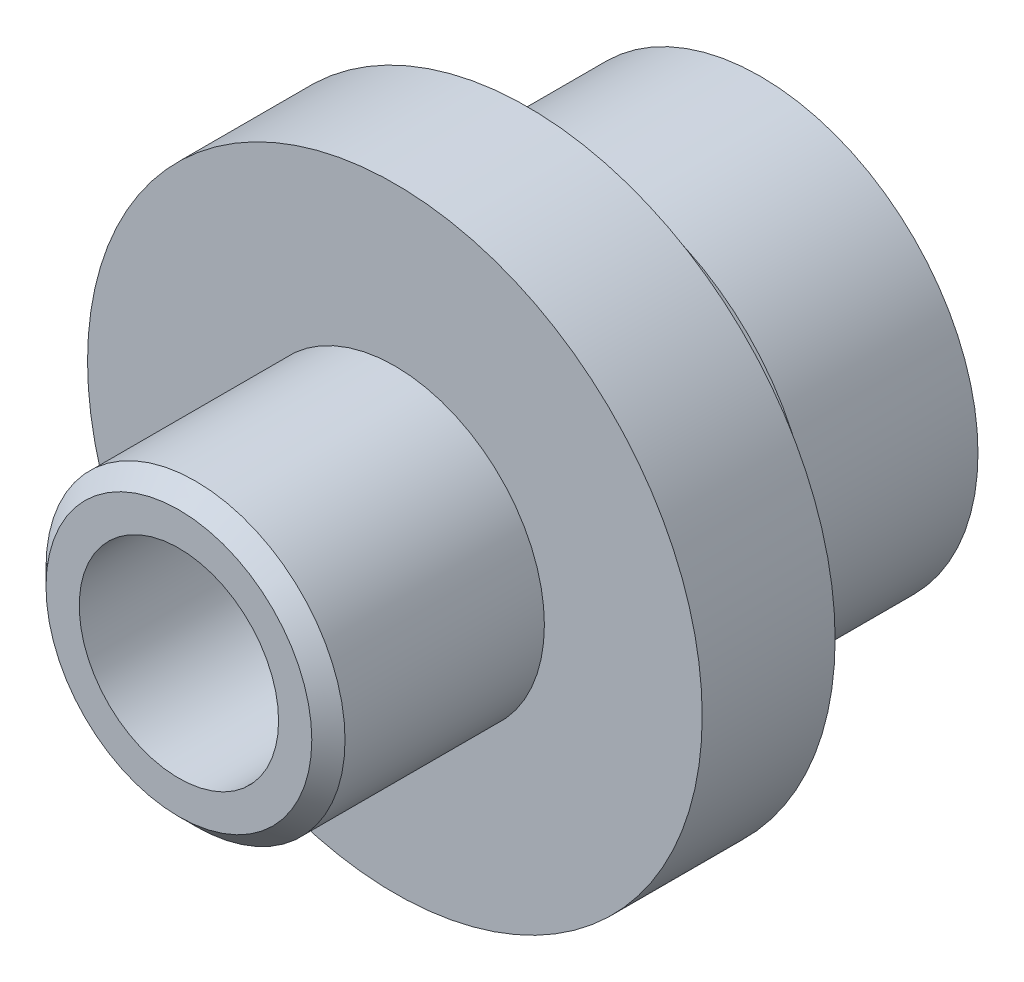
SolidWorks part; units mm, degrees
ref_plane "Front Plane" through (0, 0, 0) normal (0, 0, 1) x (1, 0, 0)
ref_plane "Top Plane" through (0, 0, 0) normal (0, 1, 0) x (1, 0, 0)
ref_plane "Right Plane" through (0, 0, 0) normal (1, 0, 0) x (0, 0, -1)
sketch "Sketch1" plane through (0, 0, 0) normal (0, 0, 1) x (1, 0, 0)
  circle A0 centre (0, 0) radius 3
  circle A1 centre (0, 0) radius 9.25
extrude "Boss-Extrude1" add sketch "Sketch1" along normal blind 17.5
sketch "Sketch2" plane through (0, 0, 17.5) normal (0, 0, 1) x (1, 0, 0)
  circle A0 centre (0, 0) radius 4.5
extrude "Cut-Extrude1" cut sketch "Sketch2" against normal blind 6.5 flip side to cut
sketch "Sketch3" plane through (0, 0, 0) normal (0, 0, -1) x (-1, 0, 0)
  circle A0 centre (0, 0) radius 6.55
extrude "Cut-Extrude2" cut sketch "Sketch3" against normal blind 7 flip side to cut
sketch "Sketch4" plane through (0, 0, 0) normal (0, 0, -1) x (-1, 0, 0)
  circle A0 centre (0, 0) radius 6
  circle A1 centre (0, 0) radius 7.5
extrude "Cut-Extrude3" cut sketch "Sketch4" against normal blind 3 from offset 5 offset against normal yes
chamfer "Chamfer1" distance 0.5 angle 45 1 edges at (4.5, 0, 17.5)
